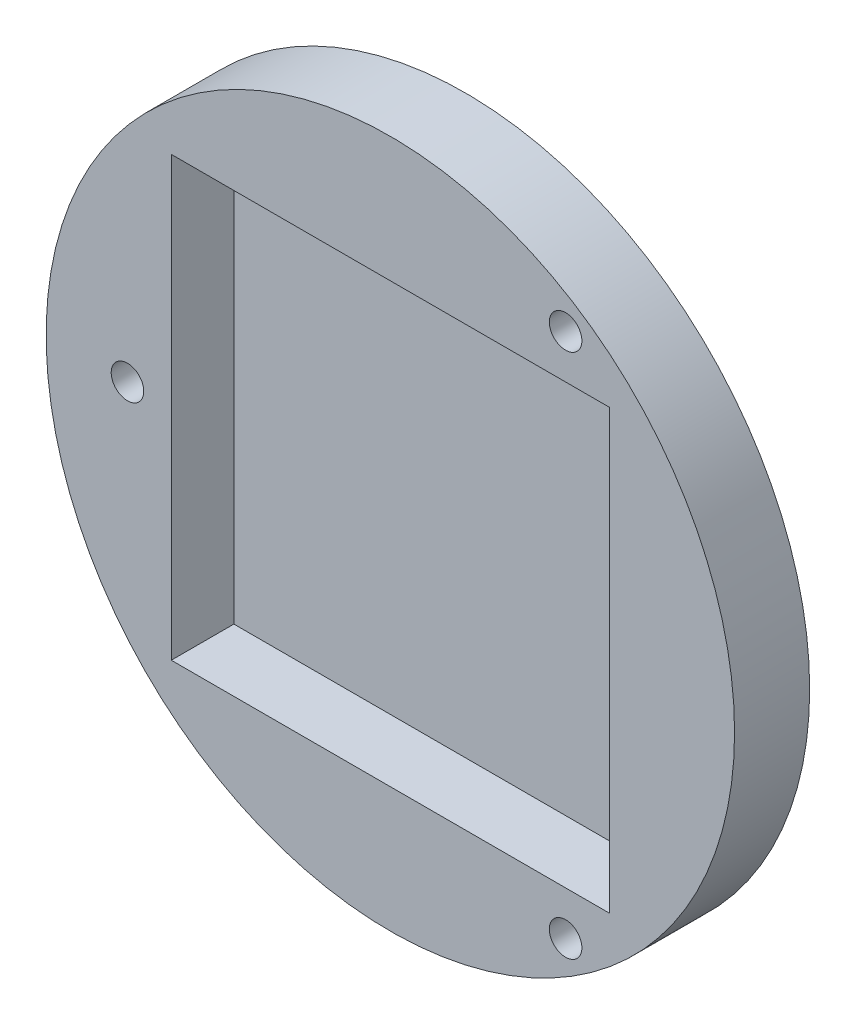
SolidWorks part; units mm, degrees
material "Nylon 101"
ref_plane "Front Plane" through (0, 0, 0) normal (0, 0, 1) x (1, 0, 0)
ref_plane "Top Plane" through (0, 0, 0) normal (0, 1, 0) x (1, 0, 0)
ref_plane "Right Plane" through (0, 0, 0) normal (1, 0, 0) x (0, 0, -1)
sketch "Sketch1" plane through (0, 0, 0) normal (0, 0, 1) x (1, 0, 0)
  line L1 (-18.5, 18.5) -> (18.5, 18.5)
  line L2 (-18.5, 18.5) -> (-18.5, -18.5)
  line L3 (-18.5, -18.5) -> (18.5, -18.5)
  line L4 (18.5, 18.5) -> (18.5, -18.5)
  line L5 (-18.5, 18.5) -> (18.5, -18.5) construction
  line L6 (-18.5, -18.5) -> (18.5, 18.5) construction
  line L7 (-17.5, 17.5) -> (17.5, 17.5)
  line L8 (-17.5, 17.5) -> (-17.5, -17.5)
  line L9 (-17.5, -17.5) -> (17.5, -17.5)
  line L10 (17.5, 17.5) -> (17.5, -17.5)
  line L11 (-17.5, 17.5) -> (17.5, -17.5) construction
  line L12 (-17.5, -17.5) -> (17.5, 17.5) construction
  circle A0 centre (0, 0) radius 27.5
  point P4 (0, 0)
  point P9 (0, 0)
  dimension "D1" = 55
  dimension "D2" = 37
  dimension "D3" = 37
  dimension "D4" = 1
  dimension "D5" = 1
extrude "Boss-Extrude1" add sketch "Sketch1" along normal blind 6 contours A0 L1 L4 L3 L2 | L4 L1 L2 L3 L7 L10 L9 L8 region at (0, 17.9767, 0) region at (-26.7222, 0, 0)
extrude "Boss-Extrude2" add sketch "Sketch1<3>" along normal blind 1 contours L10 L7 L8 L9 region at (0, 0, 0)
sketch "Sketch1<3>" plane through (0, 0, 0) normal (0, 0, 1) x (1, 0, 0) same geometry as "Sketch1"
sketch "Sketch2" plane through (0, 0, 0) normal (0, 1, 0) x (1, 0, 0)
  line L4 (0, 15) -> (0, -15) construction
  line L5 (0, 6.5) -> (0, 0)
  line L6 (0, 0) -> (-6.5, 0)
  arc A1 (0, 6.5) -> (-6.5, 0) centre (0, 0) ccw
  dimension "D1" = 13
  dimension "D4" = 30
revolve "Revolve1" add sketch "Sketch2" angle 360 about L4
hole_wizard "M2 Clearance Hole1" positions "Sketch3" profile "Sketch4" hole size "M2" standard "ANSI Metric" end condition through all
sketch "Sketch3" plane through (0, 0, 6) normal (0, 0, 1) x (1, 0, 0)
  line L0 (-17.5, 17.5) -> (-17.5, -17.5) construction
  line L1 (-17.5, -17.5) -> (17.5, -17.5) construction
  line L2 (-17.5, 17.5) -> (17.5, 17.5) construction
  line L3 (17.5, 17.5) -> (17.5, -17.5) construction
  point P0 (-21, 0)
  point P2 (14, -21)
  point P4 (14, 21)
  dimension "D1" = 3.5
  dimension "D2" = 3.5
  dimension "D3" = 3.5
  dimension "D4" = 3.5
sketch "Sketch4" plane through (-21, 0, 6) normal (1, 0, 0) x (0, -1, 0)
  line L0 (0, 0) -> (0, 12.5)
  line L1 (0, 12.5) -> (1.3, 12.5)
  line L2 (1.3, 12.5) -> (1.3, 0)
  line L5 (1.3, 0) -> (0, 0)
  line L11 (0, -6.35) -> (0, 107.95) construction
  dimension "Thru Hole Dia." = 2.6
  dimension "Thru Hole Depth" = 12.5
